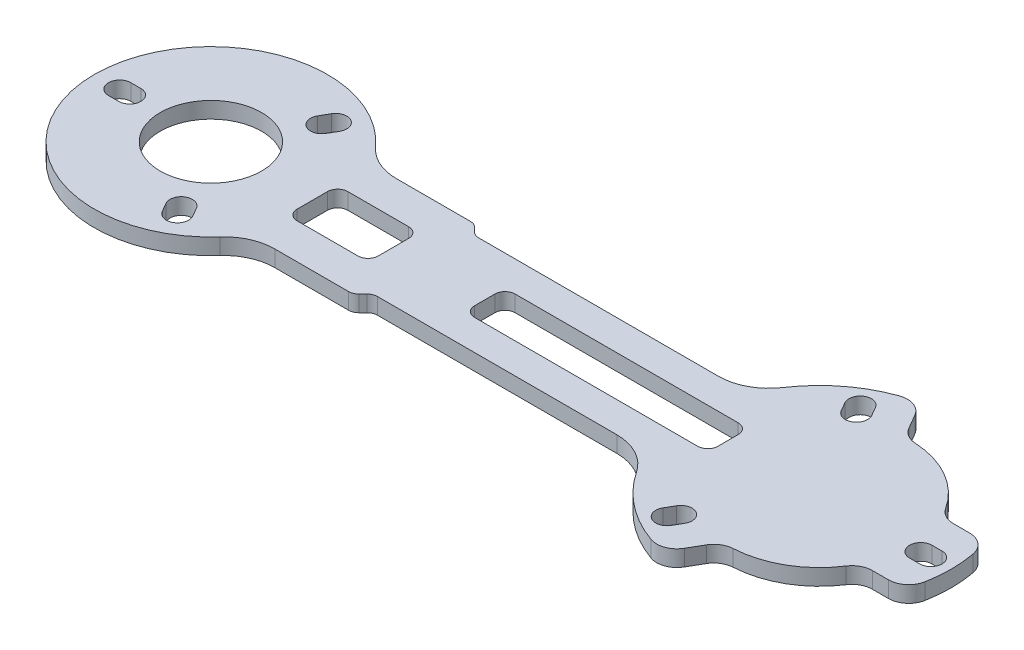
SolidWorks part; units mm, degrees
material "Thornel VCB-20 Carbon Cloth"
ref_plane "Front Plane" through (0, 0, 0) normal (0, 0, 1) x (1, 0, 0)
ref_plane "Top Plane" through (0, 0, 0) normal (0, 1, 0) x (1, 0, 0)
ref_plane "Right Plane" through (0, 0, 0) normal (1, 0, 0) x (0, 0, -1)
sketch "Sketch1" plane through (0, 0, 0) normal (0, 1, 0) x (1, 0, 0)
  line L0 (-9, 5) -> (18, 5)
  line L2 (0, 5) -> (0, -5) construction
  line L3 (-30, 0) -> (30, 0) construction
  line L4 (-20.1893, 6) -> (-10, 6)
  line L5 (-10, 6) -> (-9, 5)
  line L6 (-20.1893, -6) -> (-10, -6)
  line L7 (-10, -6) -> (-9, -5)
  line L8 (-15.0946, 6) -> (-15.0946, -6) construction
  line L9 (-9, -5) -> (18, -5)
  arc A0 (18, 5) -> (18, -5) centre (30, 0) cw
  arc A1 (-20.1893, 6) -> (-20.1893, -6) centre (-30, 0) ccw
  point P17 (-15.0946, 0)
  dimension "D1" = 10
  dimension "D3" = 23
  dimension "D4" = 26
  dimension "D2" = 60
  dimension "D5" = 45
  dimension "D6" = 45
  dimension "D7" = 12
  dimension "D8" = 10
extrude "Boss-Extrude1" add sketch "Sketch1" along normal blind 1.6
ref_axis "Axis1" through (30, -4.3921, 0) along (0, 1, 0)
ref_axis "Axis2" through (-30, -5.2731, 0) along (0, 1, 0)
sketch "Sketch2" plane through (0, 0, 0) normal (0, 1, 0) x (1, 0, 0)
  line L0 (24.75, -9.0933) -> (30, 0) construction
  line L1 (30, 0) -> (40.5, 0) construction
  line L2 (30, 0) -> (24.75, 9.0933) construction
  line L3 (40, 0) -> (41, 0) construction
  line L4 (40, 1.1) -> (41, 1.1)
  line L5 (40, -1.1) -> (41, -1.1)
  line L6 (25, -8.6603) -> (24.5, -9.5263) construction
  line L7 (25.9526, -9.2103) -> (25.4526, -10.0763)
  line L8 (24.0474, -8.1103) -> (23.5474, -8.9763)
  line L9 (25, 8.6603) -> (24.5, 9.5263) construction
  line L10 (24.0474, 8.1103) -> (23.5474, 8.9763)
  line L11 (25.9526, 9.2103) -> (25.4526, 10.0763)
  circle A3 centre (30, 0) radius 10.5 construction
  arc A4 (40, 1.1) -> (40, -1.1) centre (40, 0) ccw
  arc A5 (41, -1.1) -> (41, 1.1) centre (41, 0) ccw
  arc A6 (25.9526, -9.2103) -> (24.0474, -8.1103) centre (25, -8.6603) ccw
  arc A7 (23.5474, -8.9763) -> (25.4526, -10.0763) centre (24.5, -9.5263) ccw
  arc A8 (24.0474, 8.1103) -> (25.9526, 9.2103) centre (25, 8.6603) ccw
  arc A9 (25.4526, 10.0763) -> (23.5474, 8.9763) centre (24.5, 9.5263) ccw
  point P5 (40.5, 0)
  point P15 (24.75, -9.0933)
  point P22 (24.75, 9.0933)
  dimension "D1" = 1.1
  dimension "D2" = 21
  dimension "D3" = 120
  dimension "D4" = 120
  dimension "D5" = 1
extrude "Cut-Extrude1" cut sketch "Sketch2" along normal through all
sketch "Sketch3" plane through (0, 0, 0) normal (0, 1, 0) x (1, 0, 0)
  line L0 (-30, 0) -> (30, 0) construction
  line L1 (-38.5, 0) -> (-30, 0) construction
  line L2 (-30, 0) -> (-25.75, 7.3612) construction
  line L3 (-30, 0) -> (-25.75, -7.3612) construction
  line L4 (-26, -6.9282) -> (-25.5, -7.7942) construction
  line L5 (-25.0474, -6.3782) -> (-24.5474, -7.2442)
  line L6 (-26.9526, -7.4782) -> (-26.4526, -8.3442)
  line L7 (-38, 0) -> (-39, 0) construction
  line L8 (-38, -1.1) -> (-39, -1.1)
  line L9 (-38, 1.1) -> (-39, 1.1)
  line L10 (-26, 6.9282) -> (-25.5, 7.7942) construction
  line L11 (-26.9526, 7.4782) -> (-26.4526, 8.3442)
  line L12 (-25.0474, 6.3782) -> (-24.5474, 7.2442)
  circle A0 centre (-30, 0) radius 8.5 construction
  arc A4 (-25.0474, -6.3782) -> (-26.9526, -7.4782) centre (-26, -6.9282) ccw
  arc A5 (-26.4526, -8.3442) -> (-24.5474, -7.2442) centre (-25.5, -7.7942) ccw
  arc A6 (-38, -1.1) -> (-38, 1.1) centre (-38, 0) ccw
  arc A7 (-39, 1.1) -> (-39, -1.1) centre (-39, 0) ccw
  arc A8 (-26.9526, 7.4782) -> (-25.0474, 6.3782) centre (-26, 6.9282) ccw
  arc A9 (-24.5474, 7.2442) -> (-26.4526, 8.3442) centre (-25.5, 7.7942) ccw
  point P9 (-38.5, 0)
  point P12 (-25.75, -7.3612)
  point P24 (-25.75, 7.3612)
  dimension "D1" = 2.2
  dimension "D2" = 17
  dimension "D3" = 120
  dimension "D4" = 120
  dimension "D5" = 1
extrude "Cut-Extrude2" cut sketch "Sketch3" along normal through all
fillet "Fillet1" radius 5 4 edges at (18, 0.8, -5) (-20.1893, 0.8, -6) (-20.1893, 0.8, 6) (18, 0.8, 5)
sketch "Sketch4" plane through (0, 0, 0) normal (0, 1, 0) x (1, 0, 0)
  line L0 (-20, 0) -> (-12, 0) construction
  line L1 (-20, -2.5) -> (-12, -2.5)
  line L2 (-20, -2.5) -> (-20, 2.5)
  line L3 (-20, 2.5) -> (-12, 2.5)
  line L4 (-12, -2.5) -> (-12, 2.5)
  line L5 (-16, -2.5) -> (-16, 2.5) construction
  dimension "D1" = 8
  dimension "D2" = 5
  dimension "D3" = 16
extrude "Cut-Extrude3" cut sketch "Sketch4" along normal through all
fillet "Fillet2" radius 1 4 edges at (-12, 0.8, 2.5) (-12, 0.8, -2.5) (-20, 0.8, 2.5) (-20, 0.8, -2.5)
fillet "Fillet3" radius 1 4 edges at (-9, 0.8, -5) (-10, 0.8, -6) (-10, 0.8, 6) (-9, 0.8, 5)
sketch "Sketch5" plane through (0, 0, 0) normal (0, 1, 0) x (1, 0, 0)
  line L0 (-37.5, 12.9904) -> (-30, 0) construction
  line L1 (-30, 0) -> (-37.5, -12.9904) construction
  line L2 (-30, 0) -> (30, 0) construction
  line L3 (37, 12.1244) -> (30, 0) construction
  line L4 (30, 0) -> (37, -12.1244) construction
  circle A0 centre (-37.5, 12.9904) radius 8
  circle A1 centre (-37.5, -12.9904) radius 8
  circle A2 centre (37, -12.1244) radius 0.5
  circle A3 centre (37, 12.1244) radius 0.5
  circle A4 centre (-30, 0) radius 15 construction
  circle A5 centre (30, 0) radius 14 construction
  dimension "D5" = 16
  dimension "D6" = 30
  dimension "D7" = 28
  dimension "D8" = 1
  dimension "D1" = 120
  dimension "D2" = 120
  dimension "D3" = 120
  dimension "D4" = 120
sketch "Sketch6" plane through (0, 1.6, 0) normal (0, 1, 0) x (1, 0, 0)
  line L0 (-3, 0) -> (21, 0) construction
  line L3 (-3, 2) -> (21, 2)
  line L4 (-3, 2) -> (-3, -2)
  line L5 (-3, -2) -> (21, -2)
  line L6 (21, 2) -> (21, -2)
  line L7 (-9, 5) -> (18, 5) construction
  line L8 (-12, -1.5) -> (-12, 1.5) construction
  dimension "D2" = 9
  dimension "D1" = 9
  dimension "D3" = 3
extrude "Cut-Extrude4" cut sketch "Sketch6" against normal through all
sketch "Sketch7" plane through (0, 1.6, 0) normal (0, 1, 0) x (1, 0, 0)
  circle A0 centre (-30, 0) radius 5
  point P2 (0, 0)
  dimension "D1" = 10
extrude "Cut-Extrude5" cut sketch "Sketch7" against normal through all
fillet "Fillet4" radius 1 4 edges at (21, 0.8, -2) (21, 0.8, 2) (-3, 0.8, 2) (-3, 0.8, -2)
sketch "Sketch8" plane through (0, 1.6, 0) normal (0, 1, 0) x (1, 0, 0)
  line L0 (27.2794, 12.7121) -> (29.433, 8.9821)
  line L1 (38.0623, 4) -> (42.3693, 4)
  line L2 (30, 0) -> (24.75, 9.0933) construction
  line L3 (30, 0) -> (40.5, 0) construction
  arc A0 (29.433, 8.9821) -> (38.0623, 4) centre (30, 0) cw
  arc A2 (27.2794, 12.7121) -> (42.3693, 4) centre (30, 0) cw
  arc A3 (18, -5) -> (18, 5) centre (30, 0) ccw construction
  arc A5 (19.1908, -7.2222) -> (19.1908, 7.2222) centre (30, 0) ccw construction
  point P9 (43, 0)
  point P10 (42.0552, 4.8654)
  point P14 (43, 0)
  point P16 (35.8395, 2.921)
  point P17 (30, 5.8158)
  dimension "D3" = 9
  dimension "D1" = 4
  dimension "D2" = 4
extrude "Cut-Extrude6" cut sketch "Sketch8" against normal through all
pattern_circular "CirPattern1" count 2 every 120 about axis through (30, -4.3921, 0) along (0, 1, 0) of "Cut-Extrude6" reverse direction yes
fillet "Fillet5" radius 2 8 edges at (38.0623, 0.8, 4) (42.3693, 0.8, 4) (42.3693, 0.8, -4) (38.0623, 0.8, -4) (29.433, 0.8, -8.9821) (27.2794, 0.8, -12.7121) (27.2794, 0.8, 12.7121) (29.433, 0.8, 8.9821)
